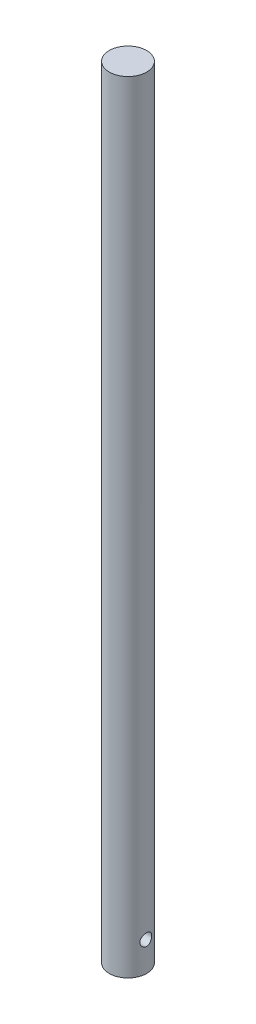
SolidWorks part; units mm, degrees
ref_plane "Front Plane" through (0, 0, 0) normal (0, 0, 1) x (1, 0, 0)
ref_plane "Top Plane" through (0, 0, 0) normal (0, 1, 0) x (1, 0, 0)
ref_plane "Right Plane" through (0, 0, 0) normal (1, 0, 0) x (0, 0, -1)
sketch "Sketch1" plane through (0, 0, 0) normal (0, 1, 0) x (1, 0, 0)
  circle A0 centre (0, 0) radius 12.7
  dimension "D1" = 25.4
extrude "Extrude1" add sketch "Sketch1" along normal blind 530
sketch "Sketch2" plane through (0, 0, 0) normal (1, 0, 0) x (0, 0, -1)
  line L0 (0, 600) -> (0, 0) construction
  circle A0 centre (0, 20) radius 4
  dimension "D1" = 8
  dimension "D2" = 20
extrude "Cut-Extrude1" cut sketch "Sketch2" against normal up to surface and the other way up to surface up to face at (0, 530, 12.7) other way up to face at (0, 530, 12.7)
